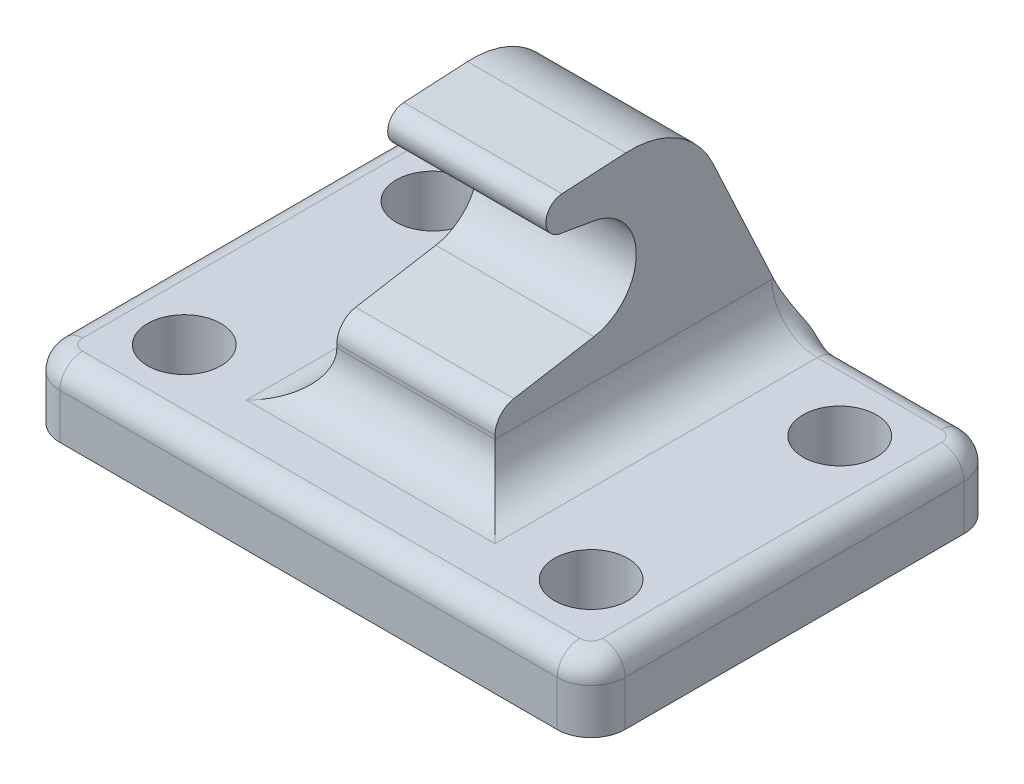
SolidWorks part; units mm, degrees
material "Nylon 6/10"
ref_plane "front" through (0, 0, 0) normal (0, 0, 1) x (1, 0, 0)
ref_plane "top" through (0, 0, 0) normal (0, 1, 0) x (1, 0, 0)
ref_plane "right" through (0, 0, 0) normal (1, 0, 0) x (0, 0, -1)
sketch "Sketch1" plane through (0, 0, 0) normal (0, 1, 0) x (1, 0, 0)
  line L1 (0, 0) -> (79.375, 0)
  line L2 (0, 0) -> (0, 57.15)
  line L3 (0, 57.15) -> (79.375, 57.15)
  line L4 (79.375, 0) -> (79.375, 57.15)
  dimension "D1" = 79.375
  dimension "D2" = 57.15
extrude "Base-Extrude" add sketch "Sketch1" along normal blind 9.525
sketch "Sketch2" plane through (0, 9.525, 0) normal (0, 1, 0) x (-1, 0, 0)
  line L0 (0, -57.15) -> (0, 0) construction
  line L1 (0, 0) -> (-79.375, 0) construction
  circle A0 centre (-11.1125, -46.0375) radius 5.1562
  circle A1 centre (-11.1125, -11.1125) radius 5.1562
  circle A2 centre (-68.2625, -11.1125) radius 5.1562
  circle A3 centre (-68.2625, -46.0375) radius 5.1562
  dimension "D1" = 10.3124
  dimension "D2" = 34.925
  dimension "D3" = 57.15
  dimension "D4" = 11.1125
  dimension "D5" = 11.1125
extrude "Cut-Extrude1" cut sketch "Sketch2" against normal through all
ref_plane "Plane4" through (39.6875, 0, 0) normal (1, 0, 0) x (0, 0, -1)
sketch "Sketch3" plane through (39.6875, 0, 0) normal (1, 0, 0) x (0, 0, -1)
  line L0 (0, 9.525) -> (57.15, 9.525) construction
  line L1 (15.0812, 9.525) -> (57.15, 9.525)
  line L2 (57.15, 9.525) -> (45.6421, 34.2125)
  line L3 (33.436, 41.5277) -> (24.4759, 41.0365)
  line L4 (24.2027, 36.312) -> (28.992, 35.4884)
  line L5 (28.9749, 21.4047) -> (17.7257, 19.4982)
  line L6 (15.0812, 16.3678) -> (15.0812, 9.525)
  line L7 (0, 9.525) -> (0, 0) construction
  arc A0 (24.4759, 41.0365) -> (24.2027, 36.312) centre (24.6062, 38.6588) ccw
  arc A1 (28.992, 35.4884) -> (28.9749, 21.4047) centre (27.7812, 28.448) cw
  arc A2 (33.436, 41.5277) -> (45.6421, 34.2125) centre (34.1313, 28.8468) cw
  arc A3 (15.0812, 16.3678) -> (17.7257, 19.4982) centre (18.2562, 16.3678) cw
  point P18 (15.0812, 19.05)
  dimension "D1" = 12.7
  dimension "D2" = 2.3813
  dimension "D3" = 7.1437
  dimension "D5" = 29.1338
  dimension "D6" = 34.1313
  dimension "D7" = 19.3218
  dimension "D9" = 18.923
  dimension "D12" = 3.175
  dimension "D4" = 24.6062
  dimension "D8" = 27.7812
  dimension "D10" = 15.0812
  dimension "D11" = 9.525
extrude "Boss-Extrude1" add sketch "Sketch3" along normal mid plane 22.225
fillet "Fillet1" radius 4.7625 4 edges at (0, 4.7625, 0) (79.375, 4.7625, 0) (0, 4.7625, -57.15) (79.375, 4.7625, -57.15)
fillet "Fillet3" radius 3.175 9 edges at (16.6687, 9.525, -57.15) (62.7062, 9.525, -57.15) (1.3949, 9.525, -55.7551) (77.9801, 9.525, -55.7551) (0, 9.525, -28.575) (79.375, 9.525, -28.575) (1.3949, 9.525, -1.3949) (77.9801, 9.525, -1.3949) (39.6875, 9.525, 0)
fillet "Fillet5" radius 6.35 5 edges at (50.8, 8.5951, -56.2201) (28.575, 8.5951, -56.2201) (50.8, 9.525, -34.5281) (39.6875, 9.525, -15.0812) (28.575, 9.525, -34.5281)
fillet "Fillet6" radius 3.175 1 edges at (39.6875, 9.525, -57.15)
